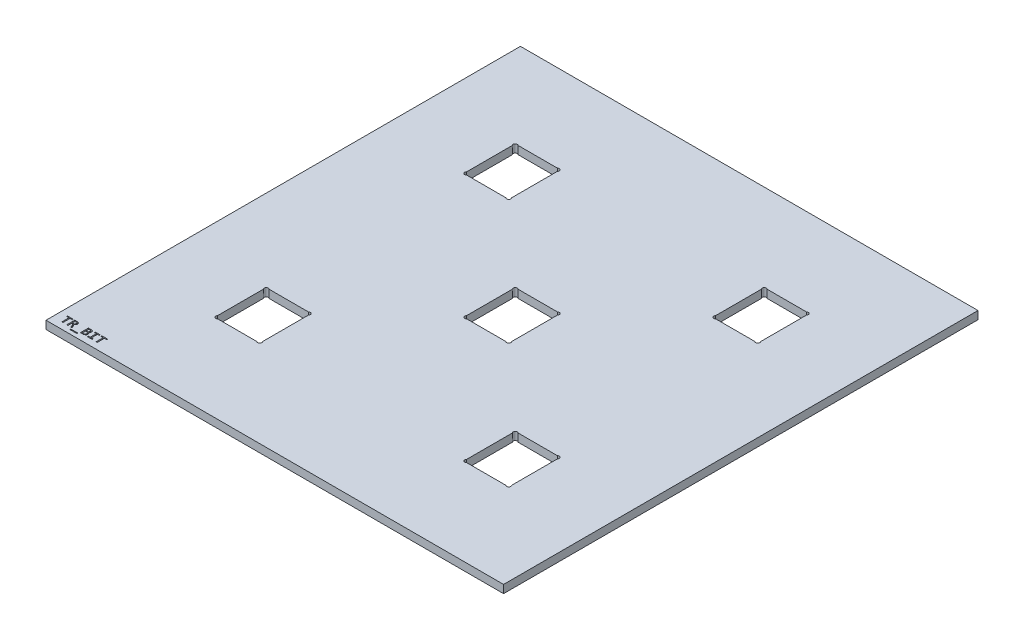
SolidWorks part; units mm, degrees
ref_plane "Front" through (0, 0, 0) normal (0, 0, 1) x (1, 0, 0)
ref_plane "Top" through (0, 0, 0) normal (0, 1, 0) x (1, 0, 0)
ref_plane "Right" through (0, 0, 0) normal (1, 0, 0) x (0, 0, -1)
sketch "Sketch1" plane through (0, 0, 0) normal (0, 1, 0) x (1, 0, 0)
  line L1 (-90.424, -93.7578) -> (90.424, -93.7578)
  line L2 (-90.424, -93.7578) -> (-90.424, 93.7578)
  line L3 (-90.424, 93.7578) -> (90.424, 93.7578)
  line L4 (90.424, -93.7578) -> (90.424, 93.7578)
  line L5 (-90.424, -93.7578) -> (90.424, 93.7578) construction
  line L6 (-90.424, 93.7578) -> (90.424, -93.7578) construction
  point P0 (0, 0)
  dimension "D1" = 180.848
  dimension "D2" = 187.5155
extrude "Boss-Extrude1" add sketch "Sketch1" along normal blind 3.175
sketch "Sketch2" plane through (0, 3.175, 0) normal (0, 1, 0) x (1, 0, 0)
  line L0 (-90.424, 93.7578) -> (90.424, -93.7578) construction
  line L2 (-8.89, -10.16) -> (8.89, -10.16)
  line L3 (-8.89, -10.16) -> (-8.89, 10.16)
  line L4 (-8.89, 10.16) -> (8.89, 10.16)
  line L5 (8.89, -10.16) -> (8.89, 10.16)
  line L6 (-8.89, -10.16) -> (8.89, 10.16) construction
  line L7 (-8.89, 10.16) -> (8.89, -10.16) construction
  point P4 (0, 0)
  point P10 (0, 0)
  dimension "D1" = 20.32
  dimension "D2" = 17.78
extrude "Cut-Extrude1" cut sketch "Sketch2" against normal blind 3.175
sketch "Sketch3" plane through (0, 3.175, 0) normal (0, 1, 0) x (1, 0, 0)
  line L0 (8.89, -10.16) -> (7.7675, -10.16) construction
  line L6 (-8.89, -10.16) -> (8.89, -10.16) construction
  line L7 (8.89, -10.16) -> (8.89, -9.0375) construction
  line L8 (8.89, -10.16) -> (8.89, 10.16) construction
  line L9 (8.89, 0) -> (-8.89, 0) construction
  line L10 (-8.89, 10.16) -> (-8.89, -10.16) construction
  line L11 (0, -10.16) -> (0, 10.16) construction
  line L12 (8.89, 10.16) -> (-8.89, 10.16) construction
  circle A4 centre (8.3287, -9.5987) radius 0.7937
  circle A5 centre (-8.3287, -9.5987) radius 0.7937
  circle A6 centre (-8.3287, 9.5987) radius 0.7937
  circle A7 centre (8.3287, 9.5987) radius 0.7937
  dimension "D1" = 1.5875
extrude "Cut-Extrude2" cut sketch "Sketch3" against normal through all
sketch "Sketch8" plane through (0, 3.175, 0) normal (0, 1, 0) x (1, 0, 0)
  line L0 (90.424, -93.7578) -> (-90.424, 93.7578) construction
  line L2 (49.2125, 49.2125) -> (-49.2125, 49.2125) construction
  line L3 (49.2125, 49.2125) -> (49.2125, -49.2125) construction
  line L4 (49.2125, -49.2125) -> (-49.2125, -49.2125) construction
  line L5 (-49.2125, 49.2125) -> (-49.2125, -49.2125) construction
  line L6 (49.2125, 49.2125) -> (-49.2125, -49.2125) construction
  line L7 (49.2125, -49.2125) -> (-49.2125, 49.2125) construction
  point P4 (0, 0)
  point P11 (-49.2125, -49.2125)
  point P12 (-49.2125, 49.2125)
  point P13 (49.2125, 49.2125)
  point P14 (49.2125, -49.2125)
  dimension "D1" = 98.425
pattern_sketch "Sketch-Pattern1" of "Cut-Extrude1", "Cut-Extrude2" driven by "Sketch8"
sketch "Sketch4" plane through (0, 3.175, 0) normal (0, 1, 0) x (1, 0, 0)
  line L0 (-87.884, -91.2177) -> (90.424, -91.2177) construction
  line L1 (-90.424, -93.7578) -> (-87.884, -93.7578) construction
  line L2 (-90.424, -93.7578) -> (-90.424, -91.2177) construction
  line L3 (-90.424, -91.2177) -> (-87.884, -91.2177) construction
  line L4 (-87.884, -93.7578) -> (-87.884, -91.2177) construction
  line L5 (90.424, -93.7578) -> (90.424, 93.7578) construction
  text T0 "TR_BIT" font "Consolas" height 3.175
  dimension "D1" = 2.54
extrude "Cut-Extrude3" cut sketch "Sketch4" against normal blind 1.5875
